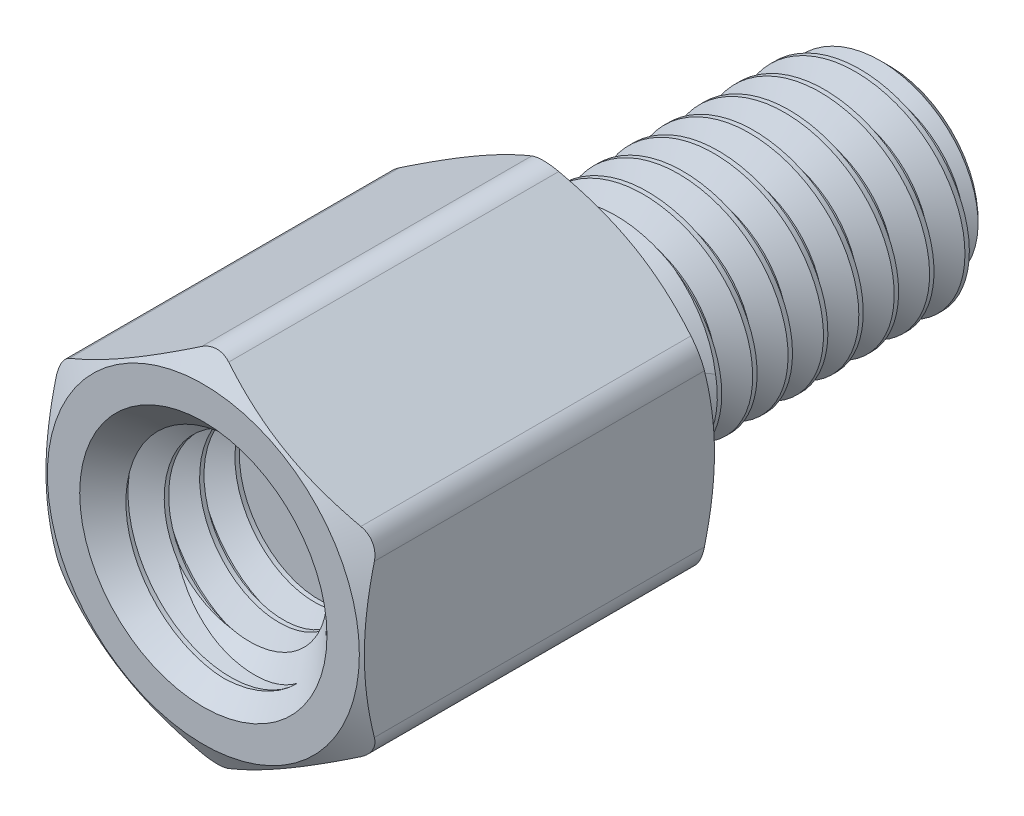
SolidWorks part; units mm, degrees
ref_plane "Front Plane" through (0, 0, 0) normal (0, 0, 1) x (1, 0, 0)
ref_plane "Top Plane" through (0, 0, 0) normal (0, 1, 0) x (1, 0, 0)
ref_plane "Right Plane" through (0, 0, 0) normal (1, 0, 0) x (0, 0, -1)
sketch "Sketch1" plane through (0, 0, 0) normal (0, 0, 1) x (1, 0, 0)
  line L1 (2.25, 1.299) -> (0, 2.5981)
  line L2 (0, 2.5981) -> (-2.25, 1.299)
  line L3 (-2.25, 1.299) -> (-2.25, -1.299)
  line L4 (-2.25, -1.299) -> (0, -2.5981)
  line L5 (0, -2.5981) -> (2.25, -1.299)
  line L6 (2.25, -1.299) -> (2.25, 1.299)
  circle A0 centre (0, 0) radius 2.25 construction
  point P10 (0, -2.25)
  dimension "Hex Size" = 4.5
sketch "Sketch2" plane through (0, 0, 0) normal (1, 0, 0) x (0, 0, -1)
  line L0 (4.7, 0) -> (-5, 0) construction
  line L2 (0, 1.5) -> (0, -1.5) construction
  line L3 (-3.2, 1.5) -> (-3.2, -1.5) construction
  line L4 (-5.4688, 1.5541) -> (-5.2188, 1.1211) construction
  line L5 (-5.2188, 1.1211) -> (-4.9688, 1.5541) construction
  line L6 (-4.9688, 1.5541) -> (-5.4688, 1.5541) construction
  line L7 (-5.4375, 1.5) -> (-5, 1.5) construction
  line L8 (-5.25, 1.1752) -> (-5.1875, 1.1752) construction
  line L9 (-5.2188, 1.1752) -> (-5.2188, 1.1211) construction
  line L10 (-5.2188, 1.5) -> (-5.2188, 1.5541) construction
  line L11 (4.6688, 1.5541) -> (5.1688, 1.5541) construction
  line L12 (5.1688, 1.5541) -> (4.9188, 1.1211) construction
  line L13 (4.9188, 1.1211) -> (4.6688, 1.5541) construction
  line L14 (4.7, 1.5) -> (5.1375, 1.5) construction
  line L15 (4.8875, 1.1752) -> (4.95, 1.1752) construction
  line L16 (4.9188, 1.1752) -> (4.9188, 1.1211) construction
  line L17 (4.9188, 1.5) -> (4.9188, 1.5541) construction
  line L18 (0, 2.5981) -> (-5, 2.5981) construction
  point P6 (0, 0)
  point P9 (-3.2, 0)
  dimension "Length" = 5
sketch "Sketch3" plane through (0, 0, 0) normal (1, 0, 0) x (0, 0, -1)
  line L0 (-3.2, 0) -> (4.7, 0)
  line L1 (-3.2, 1.5) -> (-3.2, -1.5) construction
  line L2 (4.7, 0) -> (4.7, 1.25)
  line L3 (4.7, 1.25) -> (4.45, 1.5)
  line L4 (4.45, 1.5) -> (0.7515, 1.5)
  line L5 (0.7515, 1.5) -> (0.564, 1.1752)
  line L6 (-3.2, 0) -> (-3.2, 1.25)
  line L7 (-3.2, 1.25) -> (-3.45, 1.5)
  line L8 (-3.45, 1.5) -> (-4.75, 1.5)
  line L9 (-4.75, 1.5) -> (-5, 1.75)
  line L10 (4.45, 0) -> (4.45, -1.5) construction
  line L11 (-5, 1.75) -> (-5, 2.25)
  line L12 (-5, 2.25) -> (0, 2.25)
  line L14 (0.564, 1.1752) -> (0.25, 1.1752)
  line L15 (0, 1.4252) -> (0, 2.25)
  arc A0 (0, 1.4252) -> (0.25, 1.1752) centre (0.25, 1.4252) ccw
  point P5 (-5, -2.25)
  point P8 (-3.75, -1.5)
  point P9 (3.45, -1.5)
  point P27 (0, 1.1752)
  dimension "D4" = 0.25
  dimension "D2" = 0.25
  dimension "D1" = 45
  dimension "D6" = 1.25
  dimension "D7" = 60
  dimension "D3" = 1.25
  dimension "D5" = 0.564
revolve "Revolve1" add sketch "Sketch3" angle 360 about L0 region at (0, 1.015, 0.0423)
sketch "Sketch4" plane through (0, 0, 5) normal (0, 0, 1) x (1, 0, 0)
  line L0 (0, 2.25) -> (0, 1.5) construction
  line L1 (-2.25, 1.299) -> (-2.25, -1.299)
  line L2 (-2.25, -1.299) -> (0, -2.5981)
  line L3 (0, -2.5981) -> (2.25, -1.299)
  line L4 (2.25, -1.299) -> (2.25, 1.299)
  line L5 (2.25, 1.299) -> (0, 2.5981)
  line L6 (0, 2.5981) -> (-2.25, 1.299)
  circle A0 centre (0, 0) radius 2.25 construction
  circle A1 centre (0, 0) radius 1.875
  circle A2 centre (0, 0) radius 2.25 construction
  point P16 (0, 1.875)
extrude "Boss-Extrude1" add sketch "Sketch4" against normal up to surface (5 mm away) up to face at (0, 2.25, 0)
sketch "Sketch5" plane through (0, 0, 5) normal (0, 0, 1) x (1, 0, 0)
  line L0 (-0.8604, 1.2287) -> (0.8604, -1.2287) construction
  line L1 (0, 1.5) -> (0, -1.5) construction
  line L3 (0, -2.7928) -> (0, 2.7928) construction
  circle A0 centre (0, 0) radius 2.205
  point P11 (0.8604, -1.2287)
  dimension "D1" = 4.41
  dimension "D2" = 35
extrude "Cut-Extrude1" cut sketch "Sketch5" against normal through all draft 60 flip side to cut
sketch "Sketch6" plane through (0, 0, 0) normal (0, 0, -1) x (-1, 0, 0)
  circle A0 centre (0, 0) radius 2.205
  circle A1 centre (0, 0) radius 2.205 construction
extrude "Cut-Extrude2" cut sketch "Sketch6" against normal through all draft 60 flip side to cut
fillet "Fillet1" radius 0.3825 6 edges at (0, 2.5981, 2.5) (-2.25, -1.299, 2.5) (0, -2.5981, 2.5) (2.25, -1.299, 2.5) (2.25, 1.299, 2.5) (-2.25, 1.299, 2.5)
sketch "Drawing1" plane through (0, 0, 0) normal (1, 0, 0) x (0, 0, -1)
  line L0 (-5, 1.5) -> (-3.2, 1.5) construction
  line L1 (-3.2, 1.5) -> (-3.2, -1.5) construction
  line L2 (-3.2, -1.5) -> (-5, -1.5) construction
sketch "Sketch7" plane through (0, 0, 0) normal (-1, 0, 0) x (0, 0, 1)
  line L0 (-4.8875, 1.1752) -> (-4.95, 1.1752)
  line L1 (-4.95, 1.1752) -> (-5.1531, 1.5271)
  line L2 (-5.1688, 1.5541) -> (-4.9188, 1.1211) construction
  line L3 (-5.1531, 1.5271) -> (-4.6844, 1.5271)
  line L4 (-4.9188, 1.1211) -> (-4.6688, 1.5541) construction
  line L5 (-4.6844, 1.5271) -> (-4.8875, 1.1752)
  line L6 (-4.9188, 1.5) -> (-4.9188, 1.5541) construction
  point P12 (-4.9188, 1.5271)
sketch "Sketch8" plane through (0, 0, -4.7) normal (0, 0, -1) x (-1, 0, 0)
  circle A0 centre (0, 0) radius 1.5
curve "Helix/Spiral1" pitch 0.5 height 4.559 radius 1.5 centre (0, 0, -4.7) axis (0, 0, 1) start towards (0, 1, 0)
sweep "Cut-Sweep1" cut profiles "Sketch7" path "Helix/Spiral1" align with end faces yes
sketch "Sketch9" plane through (0, 0, 3.2) normal (0, 0, 1) x (1, 0, 0)
  circle A0 centre (0, 0) radius 1.75
extrude "Boss-Extrude2" add sketch "Sketch9" along normal up to surface (1.8 mm away) up to face at (0, 1.75, 5)
sketch "Sketch10" plane through (0, 0, 0) normal (1, 0, 0) x (0, 0, -1)
  line L0 (4.7, 0) -> (-5, 0) construction
  line L1 (-3.2, 1.5) -> (-5, 1.5)
  line L2 (-3.2, 1.5) -> (-3.2, 0)
  line L3 (-3.2, 0) -> (-5, 0)
  line L4 (-5, 1.5) -> (-5, 0)
revolve "Revolve2" add sketch "Sketch10" angle 360 about L0
sketch "Sketch11" plane through (0, 0, 5) normal (0, 0, 1) x (1, 0, 0)
  circle A0 centre (0, 0) radius 1.5
  circle A1 centre (0, 0) radius 1.5 construction
sketch "Sketch12" plane through (0, 0, 0) normal (1, 0, 0) x (0, 0, -1)
  line L0 (-5.25, 1.1752) -> (-5.1875, 1.1752)
  line L1 (-5.1875, 1.1752) -> (-4.9844, 1.5271)
  line L2 (-5.2188, 1.1211) -> (-4.9688, 1.5541) construction
  line L3 (-4.9844, 1.5271) -> (-5.4531, 1.5271)
  line L4 (-5.4688, 1.5541) -> (-5.2188, 1.1211) construction
  line L5 (-5.4531, 1.5271) -> (-5.25, 1.1752)
  line L6 (-5.2188, 1.5) -> (-5.2188, 1.5541) construction
  point P12 (-5.2188, 1.5271)
curve "Helix/Spiral2" pitch 0.5 height 2.3 radius 1.5 centre (0, 0, 5) axis (0, 0, -1) start towards (0, 1, 0)
sweep "Cut-Sweep2" cut profiles "Sketch12" path "Helix/Spiral2" align with end faces yes
combine bodies "Combine1" operation type subtract main body 113 bodies to subtract 114
sketch "Sketch13" plane through (0, 0, 5) normal (0, 0, 1) x (1, 0, 0)
  circle A0 centre (0, 0) radius 1.7475
  dimension "D1" = 3.495
extrude "Cut-Extrude3" cut sketch "Sketch13" against normal through all draft 45
equation "\"Thread Pitch (B)/8@Sketch2\" = \"Thread Pitch (B)@Sketch2\" / 8"
equation "\"Thread Pitch (A)/8@Sketch2\" = \"Thread Pitch (A)@Sketch2\" / 8"
equation "\"D1@Sketch5\"=\"Hex Size@Sketch1\" * .98"
equation "\"D1@Fillet1\"=\"Hex Size@Sketch1\" * .085"
equation "\"D2@Sketch3\"=\"Thread Pitch (A)@Sketch2\" * .5"
equation "\"D4@Sketch3\" = \"D2@Sketch3\""
equation "\"D6@Sketch3\" = \"Thread Pitch (A)@Sketch2\" * 2.5"
equation "\"D3@Helix/Spiral1\" = \"Thread Length (A)@Sketch2\" - \"D5@Sketch3\" * .25"
equation "\"D4@Helix/Spiral1\" = \"Thread Pitch (A)@Sketch2\""
equation "\"D3@Sketch3\" = \"Thread Pitch (B)@Sketch2\" * 2.5"
equation "\"D5@Sketch3\" = \"Thread Length (A)@Sketch2\" * .12"
equation "\"D3@Helix/Spiral2\" = \"Minimum Thread Length (B)@Sketch2\" + \"Thread Pitch (B)@Sketch2\""
equation "\"D4@Helix/Spiral2\" = \"Thread Pitch (B)@Sketch2\""
equation "\"D1@Sketch13\"=(\"Hex Size@Sketch1\"-\"Thread Size (A)@Sketch2\")*.33+\"Thread Size (A)@Sketch2\""
